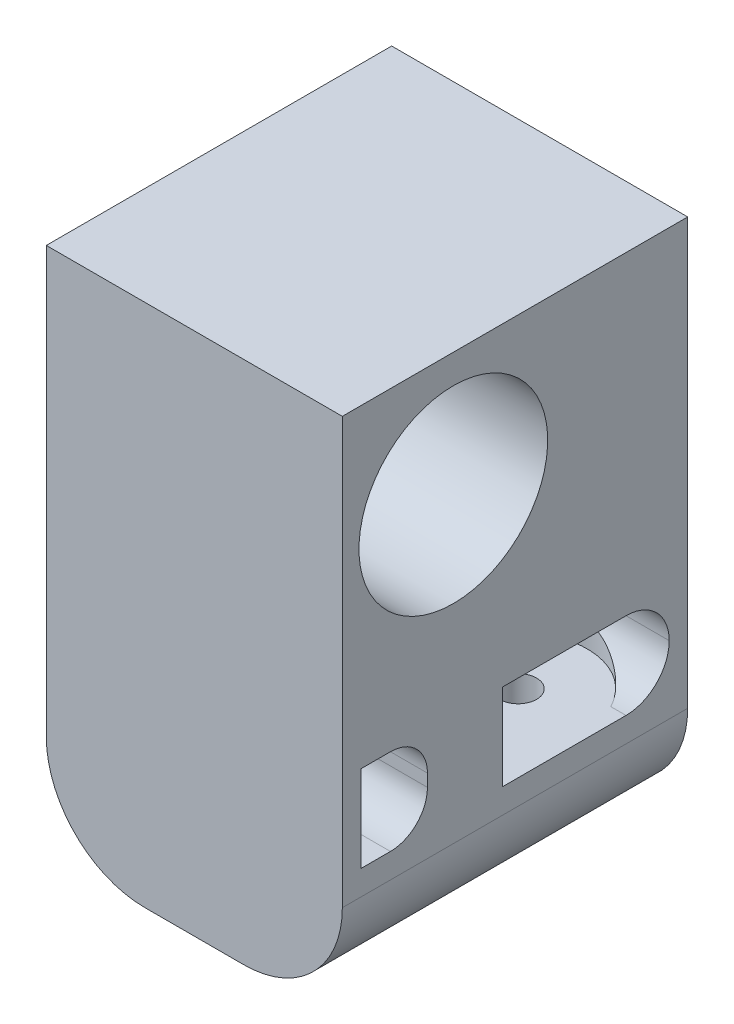
SolidWorks part; units mm, degrees
ref_plane "前视基准面" through (0, 0, 0) normal (0, 0, 1) x (1, 0, 0)
ref_plane "上视基准面" through (0, 0, 0) normal (0, 1, 0) x (1, 0, 0)
ref_plane "右视基准面" through (0, 0, 0) normal (1, 0, 0) x (0, 0, -1)
sketch "草图1" plane through (0, 0, 0) normal (0, 0, 1) x (1, 0, 0)
  line L1 (-12, 18) -> (12, 18)
  line L2 (-12, 18) -> (-12, -18)
  line L3 (-12, -18) -> (12, -18)
  line L4 (12, 18) -> (12, -18)
  line L5 (-12, 18) -> (12, -18) construction
  line L6 (-12, -18) -> (12, 18) construction
  point P0 (0, 0)
  dimension "D1" = 24
  dimension "D2" = 36
extrude "凸台-拉伸1" add sketch "草图1" along normal mid plane 38
ref_plane "基准面1" through (0, 3.5, 0) normal (0, 1, 0) x (1, 0, 0)
ref_plane "基准面2" through (0, -3.5, 0) normal (0, 1, 0) x (1, 0, 0)
sketch "草图3" plane through (0, 3.5, 0) normal (0, 1, 0) x (1, 0, 0)
  line L0 (0, 0) -> (0, -24.6721) construction
  line L1 (0, 0) -> (-19.2514, 0) construction
  line L2 (-5.75, -7.5) -> (-12, -7.5)
  line L3 (-12, -19) -> (-12, 19) construction
  line L4 (-12, -7.5) -> (-12, 19)
  line L5 (-12, 19) -> (1.75, 19)
  line L6 (12, 19) -> (-12, 19) construction
  line L7 (1.75, 19) -> (1.75, 0)
  circle A2 centre (-5.75, 0) radius 6.5 construction
  circle A3 centre (-5.75, 0) radius 5 construction
  arc A4 (-5.75, -7.5) -> (1.75, 0) centre (-5.75, 0) ccw
  dimension "D1" = 13
  dimension "D2" = 10
  dimension "D3" = 5.75
  dimension "D4" = 15
extrude "切除-拉伸2" cut sketch "草图3" against normal mid plane 7
sketch "草图4" plane through (-12, 0, 0) normal (-1, 0, 0) x (0, 0, 1)
  line L0 (13.2, -3.5) -> (-13.2, -3.5) construction
  line L1 (2.1, 0) -> (7.5, 0)
  line L2 (2.1, 0) -> (2.1, -7)
  line L3 (2.1, -7) -> (7.5, -7)
  line L4 (7.5, 0) -> (7.5, -7)
  line L5 (2.1, 0) -> (7.5, -7) construction
  line L6 (2.1, -7) -> (7.5, 0) construction
  line L7 (0, 0) -> (0, -29.9749) construction
  circle A0 centre (0, -3.5) radius 5 construction
  circle A1 centre (0, -3.5) radius 6.5 construction
  point P0 (4.8, -3.5)
  dimension "D1" = 10
  dimension "D2" = 13
  dimension "D3" = 5.4
  dimension "D4" = 7
  dimension "D5" = 4.8
extrude "切除-拉伸3" cut sketch "草图4" against normal through all
sketch "草图5" plane through (0, -3.5, 0) normal (0, 1, 0) x (1, 0, 0)
  line L0 (0, 0) -> (0, 26.819) construction
  line L1 (0, 0) -> (24.2805, 0) construction
  line L2 (0, 6.5) -> (23.2538, 6.5) construction
  line L3 (5.75, 4) -> (12, 4)
  line L4 (12, -19) -> (12, 19) construction
  line L5 (-1.75, 11.5) -> (-1.75, 19)
  line L6 (-12, 19) -> (12, 19) construction
  line L7 (-1.75, 19) -> (12, 19)
  line L8 (12, 19) -> (12, 4)
  circle A0 centre (5.75, 11.5) radius 5 construction
  circle A1 centre (5.75, 11.5) radius 6.5 construction
  arc A2 (-1.75, 11.5) -> (5.75, 4) centre (5.75, 11.5) ccw
  dimension "D2" = 10
  dimension "D3" = 13
  dimension "D5" = 15
  dimension "D1" = 6.5
  dimension "D4" = 5.75
extrude "切除-拉伸4" cut sketch "草图5" against normal mid plane 7
sketch "草图6" plane through (0, 0, -19) normal (0, 0, -1) x (-1, 0, 0)
  line L0 (0, 0) -> (0, 34.6715) construction
  line L1 (0, 0) -> (21.1433, 0) construction
  line L4 (-1.75, 7) -> (5.75, 7) construction
  circle A0 centre (0, 12) radius 4.15
  circle A1 centre (0, -12) radius 4.15
  point P2 (0, 22.7298)
  point P6 (0, 22.7298)
  dimension "D1" = 8.3
  dimension "D2" = 0
  dimension "D3" = 5
extrude "切除-拉伸5" cut sketch "草图6" against normal through all
fillet "圆角2" radius 3 2 edges at (0, -7, 2.1) (6.725, 0, 2.1)
sketch "草图10" plane through (12, 0, 0) normal (1, 0, 0) x (0, 0, -1)
  line L0 (-19, -18) -> (19, -18) construction
  line L1 (-9, -18) -> (-19, -18)
  line L2 (-9, -18) -> (-9, 18)
  line L3 (-9, 18) -> (-19, 18)
  line L4 (-19, -18) -> (-19, 18)
  dimension "D1" = 9
extrude "切除-拉伸9" cut sketch "草图10" against normal through all
sketch "草图11" plane through (-12, 0, 0) normal (-1, 0, 0) x (0, 0, 1)
  line L0 (0, 0) -> (0, -37.9964) construction
  line L2 (-19, -18) -> (9, -18)
  line L3 (9, -18) -> (9, -34.5)
  line L4 (9, -34.5) -> (-19, -34.5)
  line L5 (-19, -34.5) -> (-19, -18)
  dimension "D3" = 16.5
extrude "凸台-拉伸3" add sketch "草图11" against normal up to surface (24 mm away) up to face at (12, -3.5, 4.6929)
mirror "镜向2" about plane through (0, 0, 0) normal (0, 1, 0) of "凸台-拉伸3"
sketch "草图12" plane through (0, 0, 0) normal (0, 1, 0) x (1, 0, 0)
  line L0 (1.75, 0) -> (1.75, 28.6851) construction
  line L1 (-5.75, 5) -> (8.3291, 5) construction
  line L2 (-12, 19) -> (-1.75, 19)
  line L3 (12, 19) -> (-12, 19) construction
  line L4 (-1.75, 19) -> (-1.75, 7)
  line L5 (-1.75, 7) -> (-12, 7)
  line L6 (-0.75, 0) -> (-0.75, 28.6851) construction
  line L7 (-12, 19) -> (-12, -9) construction
  line L8 (-12, 7) -> (-12, 19)
  circle A0 centre (-5.75, 0) radius 7.5 construction
  arc A1 (1.45, -2.1) -> (1.75, 0) centre (-5.75, 0) ccw construction
  circle A2 centre (-5.75, 0) radius 6.5 construction
  circle A3 centre (-5.75, 0) radius 5 construction
  dimension "D1" = 13
  dimension "D2" = 10
  dimension "D3" = 1
  dimension "D4" = 2
extrude "凸台-拉伸4" add sketch "草图12" along normal up to surface (7 mm away) up to face at (-4.9393, 7, -4.2893)
fillet "圆角3" radius 3.5 2 edges at (-6.875, 0, -7) (-6.875, 7, -7)
sketch "草图13" plane through (0, 0, 0) normal (0, -1, 0) x (1, 0, 0)
  line L0 (12, -19) -> (1.75, -19)
  line L1 (12, -19) -> (-12, -19) construction
  line L2 (1.75, -19) -> (1.75, -17.5)
  line L3 (1.75, -17.5) -> (12, -17.5)
  line L4 (12, 9) -> (12, -19) construction
  line L5 (12, -17.5) -> (12, -19)
  line L7 (1.75, 0) -> (1.75, -5.1557) construction
  line L8 (5.75, -16.5) -> (17.8061, -16.5) construction
  circle A0 centre (5.75, -11.5) radius 7.5 construction
  arc A1 (5.75, -4) -> (1.75, -5.1557) centre (5.75, -11.5) ccw construction
  circle A2 centre (5.75, -11.5) radius 6.5 construction
  circle A3 centre (5.75, -11.5) radius 5 construction
  dimension "D1" = 10
  dimension "D2" = 13
  dimension "D3" = 0
  dimension "D4" = 1
extrude "凸台-拉伸5" add sketch "草图13" along normal up to surface (7 mm away) up to face at (4.9393, -7, -11.1893)
fillet "圆角4" radius 3.5 2 edges at (6.875, 0, -17.5) (6.875, -7, -17.5)
sketch "草图14" plane through (0, 0, 0) normal (0, -1, 0) x (1, 0, 0)
  circle A0 centre (5.75, -11.5) radius 5.6
  arc A1 (5.75, -4) -> (1.75, -5.1557) centre (5.75, -11.5) ccw construction
  dimension "D1" = 11.2
extrude "切除-拉伸10" cut sketch "草图14" along normal up to surface (7 mm away) up to face at (4.0281, -7, -11.9924)
fillet "圆角6" radius 3 1 edges at (-5.275, 0, 2.1)
sketch "草图16" plane through (0, 0, 9) normal (0, 0, 1) x (1, 0, 0)
  circle A0 centre (0, -12) radius 4.15 construction
  circle A1 centre (0, 12) radius 4.15 construction
  circle A2 centre (0, -12) radius 4.15
  circle A3 centre (0, 12) radius 4.15
extrude "凸台-拉伸6" add sketch "草图16" against normal blind 18
sketch "草图17" plane through (-12, 0, 0) normal (-1, 0, 0) x (0, 0, 1)
  line L0 (0, 0) -> (0, 30.9975) construction
  line L1 (7.5, 7) -> (-20.7528, 7) construction
  line L2 (9, -34.5) -> (9, 34.5) construction
  line L3 (-19, -34.5) -> (9, -34.5)
  line L4 (-19, -34.5) -> (-19, -17)
  line L5 (-19, -17) -> (9, -17)
  line L6 (9, -34.5) -> (9, -17)
  line L7 (7.5, -7) -> (-7.3594, -7) construction
  line L8 (-19, 34.5) -> (9, 34.5)
  line L9 (-19, 34.5) -> (-19, 25.5)
  line L10 (-19, 25.5) -> (9, 25.5)
  line L11 (9, 34.5) -> (9, 25.5)
  circle A0 centre (0, 15.5) radius 7.65
  dimension "D1" = 15.3
  dimension "D2" = 10
  dimension "D3" = 8.5
  dimension "D4" = 10
extrude "切除-拉伸11" cut sketch "草图17" against normal through all
fillet "圆角7" radius 8 2 edges at (12, -17, -5) (-12, -17, -5)
sketch "草图18" plane through (0, -17, 0) normal (0, -1, 0) x (1, 0, 0)
  circle A0 centre (-5.75, 0) radius 1.5
  arc A1 (1.75, 0) -> (-5.75, 7.5) centre (-5.75, 0) ccw construction
  dimension "D1" = 3
extrude "切除-拉伸12" cut sketch "草图18" against normal blind 26
sketch "草图19" plane through (0, -17, 0) normal (0, -1, 0) x (1, 0, 0)
  circle A0 centre (5.75, -11.5) radius 1.5
  arc A1 (1.75, -5.1557) -> (-1.75, -11.5) centre (5.75, -11.5) ccw construction
  dimension "D1" = 3
extrude "切除-拉伸13" cut sketch "草图19" against normal blind 20
sketch "草图20" plane through (0, -17, 0) normal (0, -1, 0) x (1, 0, 0)
  circle A0 centre (5.75, -11.5) radius 2.5
  circle A1 centre (-5.75, 0) radius 2.5
  circle A2 centre (-5.75, 0) radius 1.5 construction
  circle A3 centre (5.75, -11.5) radius 1.5 construction
  dimension "D1" = 5
  dimension "D2" = 5
extrude "切除-拉伸14" cut sketch "草图20" against normal blind 1
